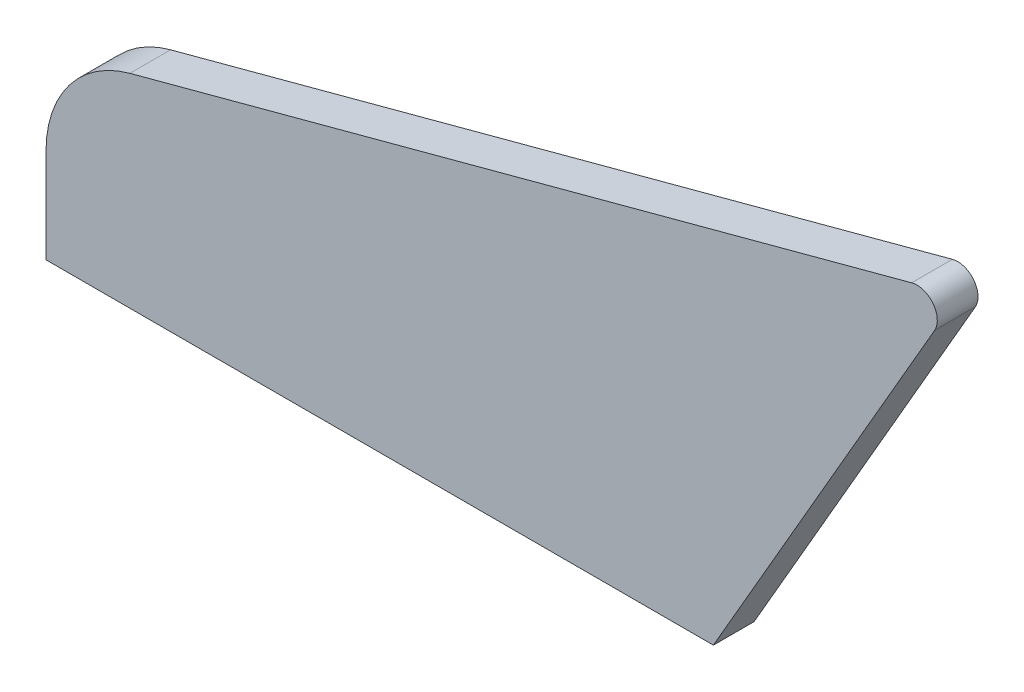
SolidWorks part; units mm, degrees
ref_plane "Plan de face" through (0, 0, 0) normal (0, 0, 1) x (1, 0, 0)
ref_plane "Plan de dessus" through (0, 0, 0) normal (0, 1, 0) x (1, 0, 0)
ref_plane "Plan de droite" through (0, 0, 0) normal (1, 0, 0) x (0, 0, -1)
sketch "Esquisse1" plane through (0, 0, 0) normal (0, 0, 1) x (1, 0, 0)
  line L0 (0, 0) -> (295, 0)
  line L1 (295, 0) -> (403.6298, 188.1523)
  line L2 (403.6298, 188.1523) -> (0, 80)
  line L3 (0, 80) -> (0, 0)
  dimension "D1" = 120
  dimension "D2" = 15
  dimension "D3" = 295
  dimension "D4" = 80
extrude "Boss.-Extru.1" add sketch "Esquisse1" along normal blind 18
fillet "Congé1" radius 50 1 edges at (0, 80, 9)
fillet "Congé2" radius 9 1 edges at (403.6298, 188.1523, 9)
